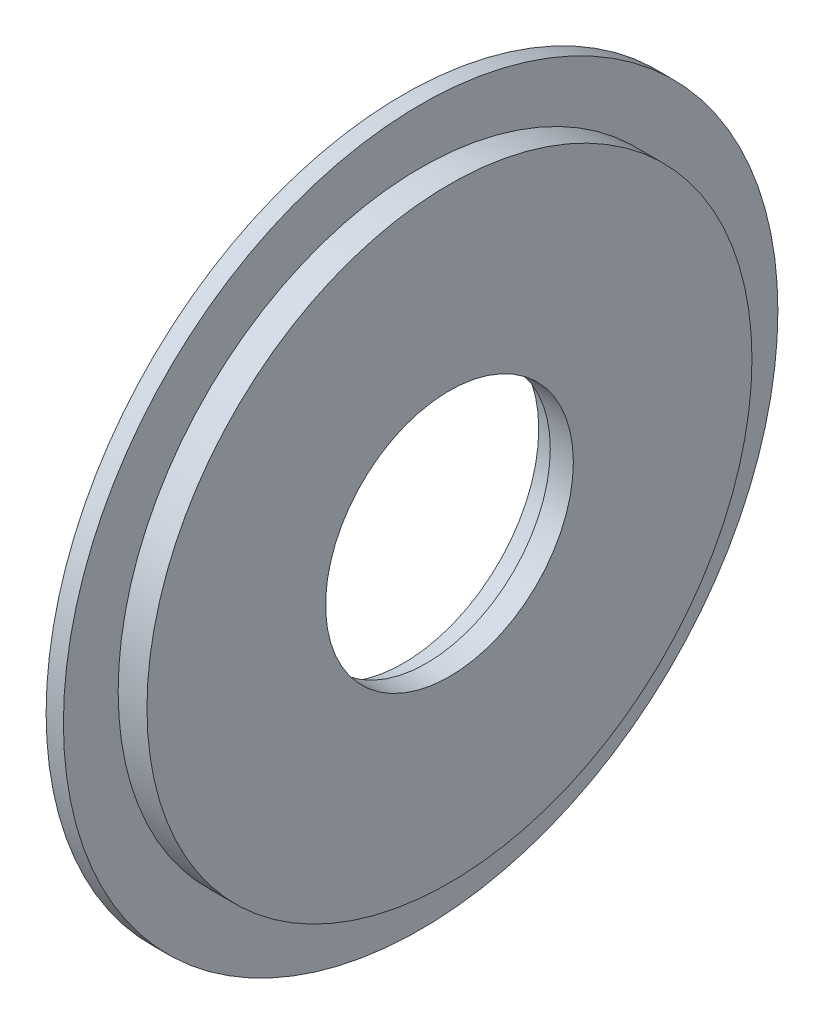
SolidWorks part; units mm, degrees
ref_plane "Alzado" through (0, 0, 0) normal (0, 0, 1) x (1, 0, 0)
ref_plane "Planta" through (0, 0, 0) normal (0, 1, 0) x (1, 0, 0)
ref_plane "Vista lateral" through (0, 0, 0) normal (1, 0, 0) x (0, 0, -1)
sketch "Croquis11" plane through (0, 0, 0) normal (1, 0, 0) x (0, 0, -1)
  circle A0 centre (0, 0) radius 62
  circle A2 centre (0, 0) radius 20
  dimension "D1" = 124
  dimension "D2" = 40
extrude "Saliente-Extruir3" add sketch "Croquis11" against normal blind 8
sketch "Croquis15" plane through (0, 0, 0) normal (1, 0, 0) x (0, 0, -1)
  circle A0 centre (0, 0) radius 21.5
  dimension "D1" = 43
extrude "Cortar-Extruir4" cut sketch "Croquis15" against normal through all
sketch "Croquis16" plane through (-8, 0, 0) normal (-1, 0, 0) x (0, 0, 1)
  circle A0 centre (0, 0) radius 23.5
  dimension "D1" = 47
extrude "Cortar-Extruir5" cut sketch "Croquis16" against normal blind 4
sketch "Croquis19" plane through (-8, 0, 0) normal (-1, 0, 0) x (0, 0, 1)
  circle A0 centre (33.6589, -17.6375) radius 3
  circle A2 centre (11.3288, -36.272) radius 3
  circle A3 centre (-17.6375, -33.6589) radius 3
  circle A4 centre (-36.272, -11.3288) radius 3
  circle A5 centre (-33.6589, 17.6375) radius 3
  circle A6 centre (-11.3288, 36.272) radius 3
  circle A7 centre (17.6375, 33.6589) radius 3
  circle A8 centre (36.272, 11.3288) radius 3
  circle A9 centre (0, 0) radius 38 construction
  point P23 (0, 0)
  dimension "D1" = 6
  dimension "D2" = 8
extrude "Cortar-Extruir8" [suppressed] cut sketch "Croquis19" against normal through all
sketch "Croquis20" [suppressed] plane through (0, 0, 0) normal (1, 0, 0) x (0, 0, -1)
  line L0 (-11.3288, -36.272) -> (0, 0) construction
  line L1 (-5.8179, -37.9932) -> (-7.0827, -32.36)
  line L2 (-7.0827, -32.36) -> (-12.5937, -30.6387)
  line L3 (-12.5937, -30.6387) -> (-16.8398, -34.5508)
  line L4 (-16.8398, -34.5508) -> (-15.5749, -40.184)
  line L5 (-15.5749, -40.184) -> (-10.064, -41.9052)
  line L6 (-10.064, -41.9052) -> (-5.8179, -37.9932)
  line L7 (-30.9791, -22.7514) -> (-27.8902, -17.8737)
  line L8 (-27.8902, -17.8737) -> (-30.5699, -12.7598)
  line L9 (-30.5699, -12.7598) -> (-36.3386, -12.5236)
  line L10 (-36.3386, -12.5236) -> (-39.4275, -17.4012)
  line L11 (-39.4275, -17.4012) -> (-36.7478, -22.5152)
  line L12 (-36.7478, -22.5152) -> (-30.9791, -22.7514)
  line L13 (-37.9932, 5.8179) -> (-32.36, 7.0827)
  line L14 (-32.36, 7.0827) -> (-30.6387, 12.5937)
  line L15 (-30.6387, 12.5937) -> (-34.5508, 16.8398)
  line L16 (-34.5508, 16.8398) -> (-40.184, 15.5749)
  line L17 (-40.184, 15.5749) -> (-41.9052, 10.064)
  line L18 (-41.9052, 10.064) -> (-37.9932, 5.8179)
  line L19 (-22.7514, 30.9791) -> (-17.8737, 27.8902)
  line L20 (-17.8737, 27.8902) -> (-12.7598, 30.5699)
  line L21 (-12.7598, 30.5699) -> (-12.5236, 36.3386)
  line L22 (-12.5236, 36.3386) -> (-17.4012, 39.4275)
  line L23 (-17.4012, 39.4275) -> (-22.5152, 36.7478)
  line L24 (-22.5152, 36.7478) -> (-22.7514, 30.9791)
  line L25 (5.8179, 37.9932) -> (7.0827, 32.36)
  line L26 (7.0827, 32.36) -> (12.5937, 30.6387)
  line L27 (12.5937, 30.6387) -> (16.8398, 34.5508)
  line L28 (16.8398, 34.5508) -> (15.5749, 40.184)
  line L29 (15.5749, 40.184) -> (10.064, 41.9052)
  line L30 (10.064, 41.9052) -> (5.8179, 37.9932)
  line L31 (30.9791, 22.7514) -> (27.8902, 17.8737)
  line L32 (27.8902, 17.8737) -> (30.5699, 12.7598)
  line L33 (30.5699, 12.7598) -> (36.3386, 12.5236)
  line L34 (36.3386, 12.5236) -> (39.4275, 17.4012)
  line L35 (39.4275, 17.4012) -> (36.7478, 22.5152)
  line L36 (36.7478, 22.5152) -> (30.9791, 22.7514)
  line L37 (37.9932, -5.8179) -> (32.36, -7.0827)
  line L38 (32.36, -7.0827) -> (30.6387, -12.5937)
  line L39 (30.6387, -12.5937) -> (34.5508, -16.8398)
  line L40 (34.5508, -16.8398) -> (40.184, -15.5749)
  line L41 (40.184, -15.5749) -> (41.9052, -10.064)
  line L42 (41.9052, -10.064) -> (37.9932, -5.8179)
  line L43 (22.7514, -30.9791) -> (17.8737, -27.8902)
  line L44 (17.8737, -27.8902) -> (12.7598, -30.5699)
  line L45 (12.7598, -30.5699) -> (12.5236, -36.3386)
  line L46 (12.5236, -36.3386) -> (17.4012, -39.4275)
  line L47 (17.4012, -39.4275) -> (22.5152, -36.7478)
  line L48 (22.5152, -36.7478) -> (22.7514, -30.9791)
  circle A0 centre (-11.3288, -36.272) radius 5 construction
  circle A3 centre (0, 0) radius 38 construction
  point P57 (0, 0)
  dimension "D1" = 10
  dimension "D2" = 8
extrude "Cortar-Extruir9" [suppressed] cut sketch "Croquis20" against normal blind 5
sketch "Croquis21" plane through (0, 0, 0) normal (1, 0, 0) x (0, 0, -1)
  circle A0 centre (0, 0) radius 52.5
  circle A1 centre (0, 0) radius 62 construction
  circle A2 centre (0, 0) radius 62
  dimension "D1" = 105
extrude "Cortar-Extruir10" cut sketch "Croquis21" against normal blind 5
sketch "Croquis22" plane through (-8, 0, 0) normal (-1, 0, 0) x (0, 0, 1)
  circle A0 centre (0, 0) radius 27.5
  circle A1 centre (0, 0) radius 30
  circle A2 centre (0, 0) radius 45
  circle A3 centre (0, 0) radius 47.5
  circle A4 centre (0, 0) radius 55
  circle A5 centre (0, 0) radius 57.5
  dimension "D1" = 55
  dimension "D2" = 60
  dimension "D3" = 90
  dimension "D4" = 95
  dimension "D5" = 110
  dimension "D6" = 115
extrude "Cortar-Extruir11" [suppressed] cut sketch "Croquis22" against normal blind 1 contours A1 A0 | A3 A2 | A5 A4
fillet "Redondeo1" [suppressed] radius 1
sketch "Croquis23" plane through (0, 0, 0) normal (0, 1, 0) x (1, 0, 0)
  line L0 (-4.4, 0) -> (4.4, 0) construction
  line L1 (-8, -4) -> (-7.75, -4)
  line L2 (-8, -4) -> (-8, 4)
  line L3 (-8, 4) -> (-7.75, 4)
  line L4 (-6.5, -2.75) -> (-6.5, 2.75)
  line L5 (-8, -4) -> (-6.5, 4) construction
  line L6 (-8, 4) -> (-6.5, -4) construction
  line L7 (-8, 62) -> (-8, -62) construction
  arc A0 (-7.75, -4) -> (-6.5, -2.75) centre (-7.75, -2.75) ccw
  arc A1 (-7.75, 4) -> (-6.5, 2.75) centre (-7.75, 2.75) cw
  point P0 (-7.25, 0)
  dimension "D3" = 1.25
  dimension "D1" = 8
  dimension "D2" = 1.5
extrude "Cortar-Extruir12" [suppressed] cut sketch "Croquis23" against normal up to surface (7.1341 mm away) from surface
